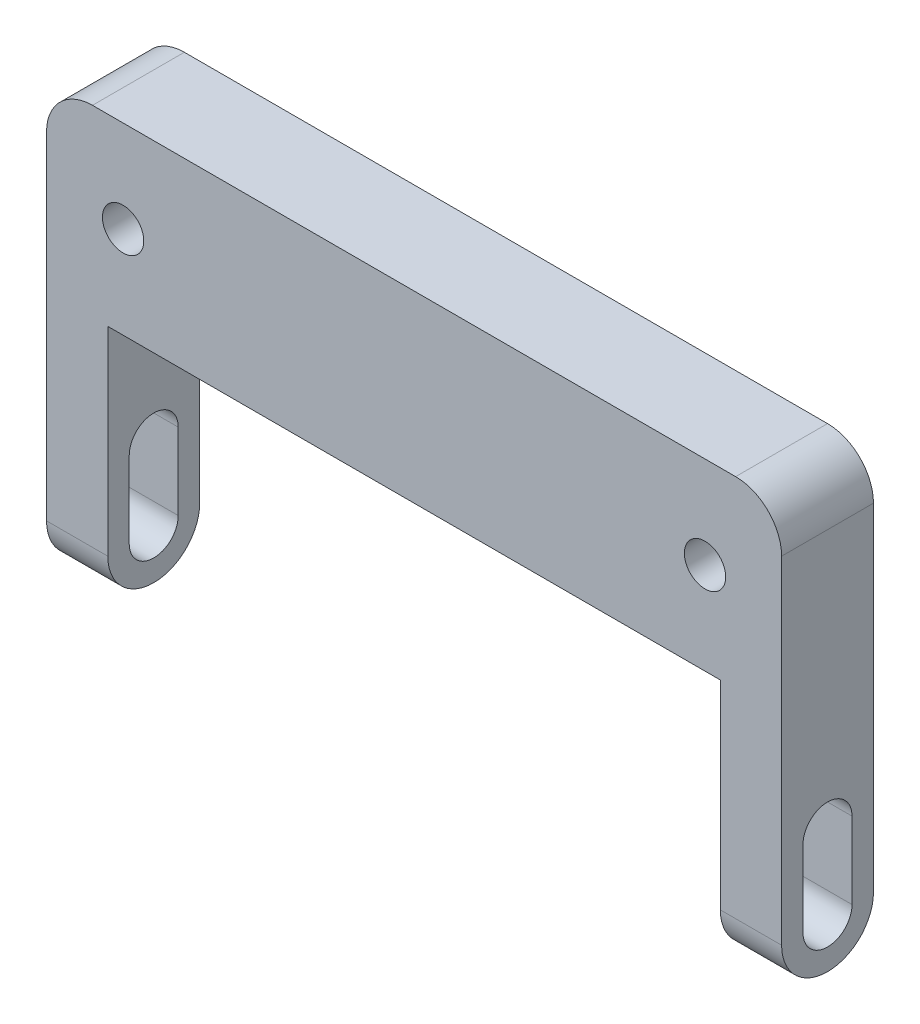
SolidWorks part; units mm, degrees
ref_plane "前基準面" through (0, 0, 0) normal (0, 0, 1) x (1, 0, 0)
ref_plane "上基準面" through (0, 0, 0) normal (0, 1, 0) x (1, 0, 0)
ref_plane "右基準面" through (0, 0, 0) normal (1, 0, 0) x (0, 0, -1)
sketch "草圖1" plane through (0, 0, 0) normal (0, 0, 1) x (1, 0, 0)
  line L1 (-20, -6) -> (20, -6)
  line L2 (-24, -6) -> (-24, 6)
  line L3 (-24, 6) -> (24, 6)
  line L4 (24, -6) -> (24, 6)
  line L5 (-24, -6) -> (24, 6) construction
  line L6 (-24, 6) -> (24, -6) construction
  line L8 (24, -6) -> (24, -22)
  line L9 (24, -22) -> (20, -22)
  line L10 (20, -6) -> (20, -22)
  line L12 (-24, -6) -> (-24, -22)
  line L13 (-24, -22) -> (-20, -22)
  line L14 (-20, -6) -> (-20, -22)
  point P0 (0, 0)
  dimension "D1" = 48
  dimension "D2" = 12
  dimension "D3" = 16
  dimension "D4" = 4
extrude "填料-伸長1" add sketch "草圖1" along normal blind 6
sketch "草圖2" plane through (24, 0, 0) normal (1, 0, 0) x (0, 0, -1)
  line L0 (-3, -22) -> (-3, -19) construction
  line L1 (-6, -22) -> (0, -22) construction
  line L2 (-1.4, -14) -> (-1.4, -19)
  line L3 (-4.6, -14) -> (-4.6, -19)
  arc A0 (-4.6, -19) -> (-1.4, -19) centre (-3, -19) ccw
  arc A1 (-1.4, -14) -> (-4.6, -14) centre (-3, -14) ccw
  dimension "D1" = 3.2
  dimension "D2" = 3
  dimension "D3" = 5
extrude "除料-伸長1" cut sketch "草圖2" against normal up to next
mirror "鏡射1" about plane through (0, 0, 0) normal (1, 0, 0) of "除料-伸長1"
fillet "圓角1" radius 3 6 edges at (-24, 6, 3) (24, 6, 3) (-22, -22, 6) (-22, -22, 0) (22, -22, 0) (22, -22, 6)
sketch "草圖3" plane through (0, 0, 0) normal (0, 0, -1) x (-1, 0, 0)
  circle A0 centre (19, 0) radius 1.35
  circle A1 centre (-19, 0) radius 1.35
  dimension "D1" = 2.7
  dimension "D2" = 38
  dimension "D3" = 19
extrude "除料-伸長2" cut sketch "草圖3" against normal through all
